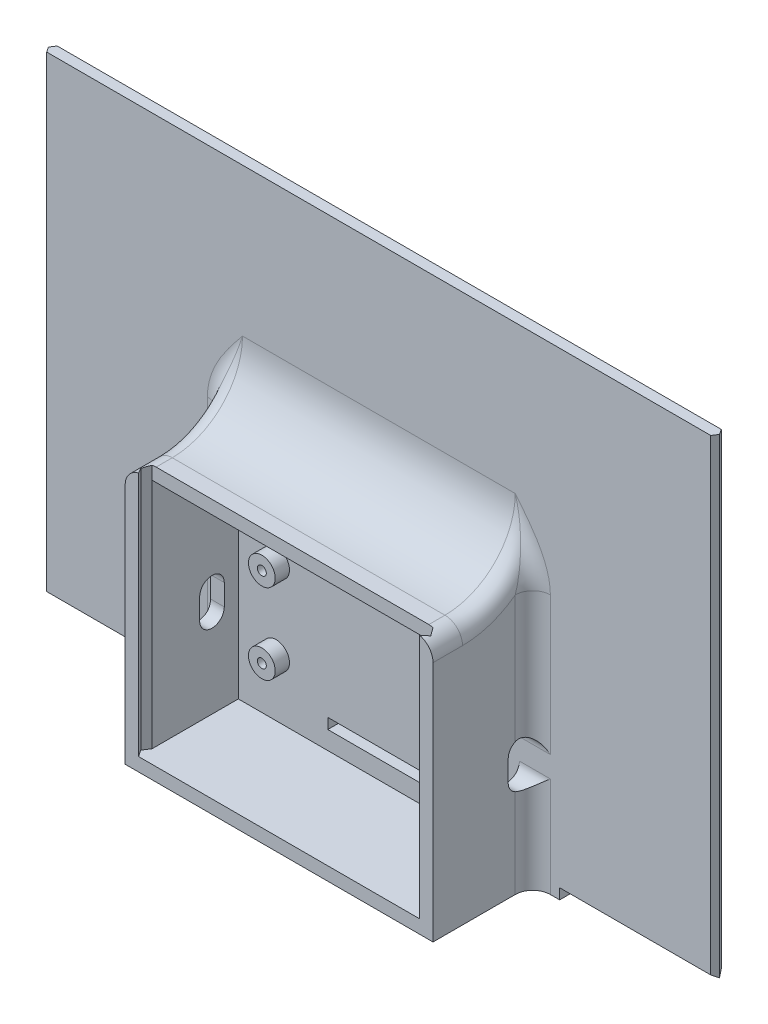
SolidWorks part; units mm, degrees
ref_plane "Front Plane" through (0, 0, 0) normal (0, 0, 1) x (1, 0, 0)
ref_plane "Top Plane" through (0, 0, 0) normal (0, 1, 0) x (1, 0, 0)
ref_plane "Right Plane" through (0, 0, 0) normal (1, 0, 0) x (0, 0, -1)
sketch "Sketch1" plane through (0, 0, 0) normal (0, 0, 1) x (1, 0, 0)
  line L1 (85.5, -56) -> (-85.5, -56)
  line L2 (85.5, -56) -> (85.5, 56)
  line L3 (85.5, 56) -> (-85.5, 56)
  line L4 (-85.5, -56) -> (-85.5, 56)
  line L5 (85.5, -56) -> (-85.5, 56) construction
  line L6 (85.5, 56) -> (-85.5, -56) construction
  line L11 (80, -45) -> (-80, -45)
  line L12 (80, -45) -> (80, 51)
  line L13 (80, 51) -> (-80, 51)
  line L14 (-80, -45) -> (-80, 51)
  line L15 (80, -45) -> (-80, 51) construction
  line L16 (80, 51) -> (-80, -45) construction
  line L17 (-14.5, -56) -> (14.5, -56)
  line L18 (-14.5, -56) -> (-14.5, -59)
  line L19 (-14.5, -59) -> (14.5, -59)
  line L20 (14.5, -56) -> (14.5, -59)
  line L21 (97.5, 68) -> (-97.5, 68)
  line L22 (97.5, 68) -> (97.5, -68)
  line L23 (97.5, -68) -> (-97.5, -68)
  line L24 (-97.5, 68) -> (-97.5, -68)
  line L25 (97.5, 68) -> (-97.5, -68) construction
  line L26 (97.5, -68) -> (-97.5, 68) construction
  point P0 (0, 0)
  point P6 (0, 0)
  point P7 (0, 3)
  point P16 (0, 0)
  dimension "D1" = 171
  dimension "D2" = 112
  dimension "D3" = 96
  dimension "D4" = 160
  dimension "D5" = 5
  dimension "D6" = 71
  dimension "D7" = 29
  dimension "D8" = 3
  dimension "D9" = 12
  dimension "D10" = 17.5
  dimension "D11" = 12
extrude "Boss-Extrude1" add sketch "Sketch1" against normal blind 1.5 contours L4 L1 L2 L3 L11 L14 L13 L12 | L21 L24 L23 L22 L1 L20 L19 L18 L4 L3 L2 | L14 L11 L12 L13 region at (50, -53.9559, 0) region at (0, 3, 0) region at (95.1226, 0, 0)
extrude "Boss-Extrude2" add sketch "Sketch1<3>" along normal blind 1.5 contours L21 L24 L23 L22 L1 L20 L19 L18 L4 L3 L2 | L4 L1 L2 L3 L11 L14 L13 L12 | L14 L11 L12 L13 region at (50, -53.9559, 0) region at (0, 3, 0) region at (95.1226, 0, 0)
sketch "Sketch1<3>" plane through (0, 0, 0) normal (0, 0, 1) x (1, 0, 0) same geometry as "Sketch1"
sketch "Sketch2" plane through (0, 0, 1.5) normal (0, 0, 1) x (1, 0, 0)
  line L0 (97.5, 68) -> (-97.5, 68) construction
  line L1 (90.5, -61) -> (-90.5, -61) construction
  line L2 (90.5, -61) -> (90.5, 61) construction
  line L3 (90.5, 61) -> (-90.5, 61) construction
  line L4 (-90.5, -61) -> (-90.5, 61) construction
  line L5 (90.5, -61) -> (-90.5, 61) construction
  line L6 (90.5, 61) -> (-90.5, -61) construction
  line L7 (-97.5, 68) -> (-97.5, -68) construction
  line L8 (-90.5, 61) -> (-30.1667, 61) construction
  line L9 (-30.1667, 61) -> (30.1667, 61) construction
  line L10 (30.1667, 61) -> (90.5, 61) construction
  circle A0 centre (-90.5, 61) radius 3.175
  circle A2 centre (90.5, 61) radius 3.175
  circle A3 centre (90.5, -61) radius 3.175
  circle A5 centre (-90.5, -61) radius 3.175
  circle A6 centre (-90.5, 0) radius 3.175
  circle A7 centre (30.1667, 61) radius 3.175
  circle A8 centre (90.5, 0) radius 3.175
  circle A9 centre (30.1667, -61) radius 3.175
  circle A10 centre (-30.1667, -61) radius 3.175
  circle A11 centre (-30.1667, 61) radius 3.175
  point P0 (0, 0)
  dimension "D1" = 6.35
  dimension "D2" = 7
  dimension "D3" = 7
extrude "Cut-Extrude1" [suppressed] cut sketch "Sketch2" against normal through all
sketch "Sketch3" plane through (0, 0, 1.5) normal (0, 0, 1) x (1, 0, 0)
  line L0 (-14.5, -59) -> (14.5, -59) construction
  line L1 (29.21, -48) -> (-29.21, -48) construction
  line L2 (29.21, -48) -> (29.21, -25.14) construction
  line L3 (29.21, -25.14) -> (-29.21, -25.14) construction
  line L4 (-29.21, -48) -> (-29.21, -25.14) construction
  line L5 (29.21, -48) -> (-29.21, -25.14) construction
  line L6 (29.21, -25.14) -> (-29.21, -48) construction
  line L11 (-12.1109, -48) -> (11.8889, -48) construction
  line L13 (-12.1109, -48) -> (-12.1109, -44) construction
  line L14 (-12.1109, -44) -> (11.8889, -44) construction
  line L15 (11.8889, -48) -> (11.8889, -44) construction
  line L16 (14.5, -56) -> (-14.5, -56) construction
  circle A0 centre (-29.21, -48) radius 3.81
  circle A1 centre (-29.21, -48) radius 1.27
  point P17 (-29.21, -25.14)
  point P18 (29.21, -25.14)
  point P21 (0, -56)
  point P22 (0, -48)
  point P24 (29.21, -48)
  dimension "D1" = 2.54
  dimension "D2" = 7.62
  dimension "D3" = 58.42
  dimension "D4" = 22.86
  dimension "D5" = 4
  dimension "D6" = 15
extrude "Boss-Extrude3" add sketch "Sketch3" along normal blind 4.064
pattern_sketch "Sketch-Pattern1" of "Boss-Extrude3" driven by "Sketch3"
sketch "Sketch4" plane through (0, 0, 1.5) normal (0, 0, 1) x (1, 0, 0)
  line L0 (97.5, -68) -> (-97.5, -68) construction
  line L1 (-43.7745, 5.86) -> (43.8555, 5.86)
  line L2 (-43.7745, 5.86) -> (-43.7745, -68)
  line L3 (-43.7745, -68) -> (43.8555, -68)
  line L4 (43.8555, 5.86) -> (43.8555, -68)
  line L5 (-43.7745, 5.86) -> (43.8555, -68) construction
  line L6 (-43.7745, -68) -> (43.8555, 5.86) construction
  line L8 (40.0455, -64.19) -> (-39.9645, -64.19)
  line L9 (40.0455, -64.19) -> (40.0455, 2.05)
  line L10 (40.0455, 2.05) -> (-39.9645, 2.05)
  line L11 (-39.9645, -64.19) -> (-39.9645, 2.05)
  line L12 (40.0455, -64.19) -> (-39.9645, 2.05) construction
  line L13 (40.0455, 2.05) -> (-39.9645, -64.19) construction
  circle A0 centre (-29.21, -25.14) radius 1.27 construction
  point P0 (0.0405, -31.07)
  point P7 (0.0405, -31.07)
  dimension "D1" = 3.81
  dimension "D2" = 3.81
  dimension "D3" = 80.01
  dimension "D4" = 31
extrude "Boss-Extrude4" add sketch "Sketch4" along normal blind 28.4
fillet "Fillet1" radius 20 1 edges at (0.0405, 5.86, 1.5)
fillet "Fillet2" radius 5 6 edges at (43.8555, 5.86, 25.7) (-43.7745, 5.86, 25.7) (43.8555, 11.7179, 7.3579) (-43.7745, 11.7179, 7.3579) (43.8555, -21.07, 1.5) (-43.7745, -21.07, 1.5)
sketch "Sketch5" plane through (0, 0, 29.9) normal (0, 0, 1) x (1, 0, 0)
  line L1 (40.0455, 2.05) -> (-39.9071, 2.05)
  line L2 (40.0455, 2.05) -> (40.0455, 7.3089)
  line L3 (40.0455, 7.3089) -> (-39.9071, 7.3089)
  line L4 (-39.9071, 2.05) -> (-39.9071, 7.3089)
extrude "Cut-Extrude2" cut sketch "Sketch5" against normal blind 3.81
sketch "Sketch6" plane through (0, -64.19, 0) normal (0, 1, 0) x (1, 0, 0)
  line L0 (-39.9645, -29.9) -> (40.0455, -29.9) construction
  line L1 (41.3155, -26.09) -> (-41.2345, -26.09)
  line L2 (41.3155, -26.09) -> (41.3155, -29.9)
  line L3 (41.3155, -29.9) -> (-41.2345, -29.9)
  line L4 (-41.2345, -26.09) -> (-41.2345, -29.9)
  line L6 (-39.9645, -29.9) -> (-39.9645, -1.5) construction
  line L7 (40.0455, -29.9) -> (40.0455, -1.5) construction
  line L8 (41.3155, -27.995) -> (40.0455, -29.9)
  line L9 (41.3155, -27.995) -> (40.0455, -26.09)
  line L10 (-41.2345, -27.995) -> (-39.9645, -29.9)
  line L11 (-41.2345, -27.995) -> (-39.9645, -26.09)
  line M6 (-39.9645, -1.5) -> (-39.9645, -29.9)
  line M7 (-39.9645, -29.9) -> (40.0455, -29.9)
  line M8 (40.0455, -29.9) -> (40.0455, -1.5)
  dimension "D1" = 3.81
  dimension "D2" = 0
  dimension "D3" = 1.27
  dimension "D4" = 1.27
extrude "Cut-Extrude3" cut sketch "Sketch6" along normal through all contours L1 M8 M6 M7 | L8 L9 M8 | L11 L10 M6 region at (0.0405, -64.19, 27.995) region at (40.4688, -64.19, 27.995) region at (-40.3878, -64.19, 27.995)
sketch "Sketch8" plane through (0, -68, 0) normal (0, -1, 0) x (1, 0, 0)
  line L0 (-48.7745, 1.5) -> (-97.5, 1.5) construction
  line L1 (-97.5, -1.5) -> (-94.5, -1.5)
  line L2 (-97.5, -1.5) -> (-97.5, 1.5)
  line L3 (-97.5, 1.5) -> (-94.5, 1.5)
  line L4 (-94.5, -1.5) -> (-94.5, 1.5)
  line L5 (-94.5, 1.5) -> (-95.5, 0)
  line L6 (-94.5, 1.5) -> (-95.5, 1.5)
  line L7 (-94.5, 1.5) -> (-94.5, -1.5)
  line L8 (-94.5, -1.5) -> (-95.5, -1.5)
  line L9 (-95.5, 1.5) -> (-95.5, -1.5)
  line L10 (-95.5, 0) -> (-94.5, -1.5)
  line M13 (-48.7745, 1.5) -> (-97.5, 1.5)
  line M14 (-97.5, 1.5) -> (-97.5, -1.5)
  line M15 (-97.5, -1.5) -> (97.5, -1.5)
  dimension "D1" = 1
  dimension "D2" = 3
extrude "Cut-Extrude4" cut sketch "Sketch8" against normal through all contours L9 L5 M13 | L10 L9 L1 | L9 L3 M14 M15 region at (-96.5, -68, 0) region at (-95.1667, -68, -1) region at (-95.1667, -68, 1)
sketch "Sketch9" plane through (97.5, 0, 0) normal (1, 0, 0) x (0, 0, -1)
  line L0 (1.5, 68) -> (1.5, -68) construction
  line L1 (-1.5, -68) -> (1.5, -68)
  line L2 (-1.5, -68) -> (-1.5, -65)
  line L3 (-1.5, -65) -> (1.5, -65)
  line L4 (1.5, -68) -> (1.5, -65)
  line L5 (-1.5, -65) -> (0, -66)
  line L6 (-1.5, -65) -> (1.5, -65)
  line L7 (-1.5, -65) -> (-1.5, -66)
  line L8 (-1.5, -66) -> (1.5, -66)
  line L9 (1.5, -65) -> (1.5, -66)
  line L10 (0, -66) -> (1.5, -65)
  line M7 (-1.5, 68) -> (-1.5, -68)
  line M8 (-1.5, -68) -> (1.5, -68)
  line M9 (1.5, -68) -> (1.5, 68)
  dimension "D1" = 1
  dimension "D2" = 3
extrude "Cut-Extrude5" cut sketch "Sketch9" against normal blind 46 contours L8 L2 M8 M9 | L8 L5 M7 | L10 L8 L4 region at (97.5, -67, 0) region at (97.5, -65.6667, 1) region at (97.5, -65.6667, -1)
mirror "Mirror1" about plane through (0, 0, 0) normal (1, 0, 0) of "Cut-Extrude5", "Cut-Extrude4"
sketch "Sketch10" plane through (-43.7745, 0, 0) normal (-1, 0, 0) x (0, 0, 1)
  line L0 (9, -33.5) -> (9, -39.5) construction
  line L1 (12.5, -33.5) -> (12.5, -39.5)
  line L2 (5.5, -33.5) -> (5.5, -39.5)
  line L3 (6.5, 5.86) -> (6.5, -68) construction
  line L4 (29.9, -68) -> (6.5, -68) construction
  arc A0 (12.5, -33.5) -> (5.5, -33.5) centre (9, -33.5) ccw
  arc A1 (5.5, -39.5) -> (12.5, -39.5) centre (9, -39.5) ccw
  point P2 (9, -36.5)
  point P9 (0, 0)
  point P12 (9, -30)
  point P13 (9, -43)
  dimension "D1" = 7
  dimension "D2" = 6
  dimension "D3" = 2.5
  dimension "D4" = 31.5
  dimension "D5" = 13
extrude "Cut-Extrude6" cut sketch "Sketch10" against normal blind 10 and the other way blind 10
sketch "Sketch12" plane through (43.8555, 0, 0) normal (1, 0, 0) x (0, 0, -1)
  line L0 (-5, -39.5) -> (-5, -33.5) construction
  line L1 (-8.5, -39.5) -> (-8.5, -33.5)
  line L2 (-1.5, -39.5) -> (-1.5, -33.5)
  line L3 (-29.9, -68) -> (-6.5, -68) construction
  line L4 (-1.5, 5.86) -> (-1.5, -68) construction
  arc A0 (-8.5, -39.5) -> (-1.5, -39.5) centre (-5, -39.5) ccw
  arc A1 (-1.5, -33.5) -> (-8.5, -33.5) centre (-5, -33.5) ccw
  point P2 (-5, -36.5)
  point P7 (-5, -43)
  point P8 (-5, -30)
  dimension "D1" = 7
  dimension "D2" = 6
  dimension "D3" = 13
  dimension "D4" = 31.5
  dimension "D5" = 3.5
extrude "Cut-Extrude7" cut sketch "Sketch12" against normal blind 10 and the other way blind 10
